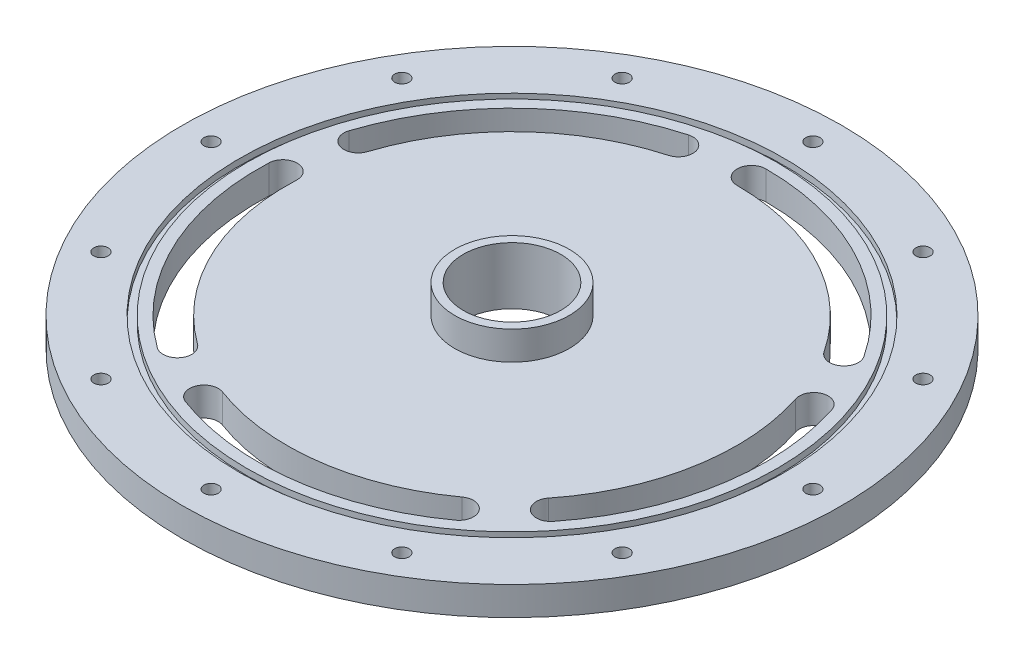
SolidWorks part; units mm, degrees
ref_plane "Front Plane" through (0, 0, 0) normal (0, 0, 1) x (1, 0, 0)
ref_plane "Top Plane" through (0, 0, 0) normal (0, 1, 0) x (1, 0, 0)
ref_plane "Right Plane" through (0, 0, 0) normal (1, 0, 0) x (0, 0, -1)
sketch "Sketch1" plane through (0, 0, 0) normal (0, 1, 0) x (1, 0, 0)
  circle A0 centre (0, 0) radius 146.05
  circle A1 centre (0, 0) radius 21.59
  circle A2 centre (0, 133.35) radius 3.175
  circle A3 centre (66.675, 115.4845) radius 3.175
  circle A4 centre (115.4845, 66.675) radius 3.175
  circle A5 centre (133.35, 0) radius 3.175
  circle A6 centre (115.4845, -66.675) radius 3.175
  circle A7 centre (66.675, -115.4845) radius 3.175
  circle A8 centre (0, -133.35) radius 3.175
  circle A9 centre (-66.675, -115.4845) radius 3.175
  circle A10 centre (-115.4845, -66.675) radius 3.175
  circle A11 centre (-133.35, 0) radius 3.175
  circle A12 centre (-115.4845, 66.675) radius 3.175
  circle A13 centre (-66.675, 115.4845) radius 3.175
  point P4 (0, 133.35)
  point P31 (0, 0)
  dimension "D1" = 292.1
  dimension "D2" = 43.18
  dimension "D4" = 6.35
  dimension "D3" = 133.35
  dimension "D5" = 12
extrude "Boss-Extrude1" add sketch "Sketch1" along normal blind 12.7
sketch "Sketch2" plane through (0, 12.7, 0) normal (0, 1, 0) x (1, 0, 0)
  circle A0 centre (0, 0) radius 120.65
  circle A1 centre (0, 0) radius 117.475
  dimension "D1" = 241.3
  dimension "D2" = 234.95
extrude "Cut-Extrude1" cut sketch "Sketch2" against normal blind 2.794
sketch "Sketch3" plane through (0, 12.7, 0) normal (0, 1, 0) x (1, 0, 0)
  line L0 (0, 0) -> (83.1307, 55.1686) construction
  arc A0 (0, 106.1466) -> (88.4428, 58.6939) centre (0, 0) cw construction
  arc A1 (93.7549, 62.2192) -> (0, 112.522) centre (0, 0) ccw
  arc A2 (83.1307, 55.1686) -> (0, 99.7712) centre (0, 0) ccw
  arc A3 (83.1307, 55.1686) -> (93.7549, 62.2192) centre (88.4428, 58.6939) ccw
  arc A4 (0, 112.522) -> (0, 99.7712) centre (0, 106.1466) ccw
  arc A5 (78.1573, -62.014) -> (94.888, 30.831) centre (0, 0) ccw
  arc A6 (78.1573, -62.014) -> (88.1458, -69.9394) centre (83.1515, -65.9767) ccw
  arc A7 (107.0148, 34.7712) -> (94.888, 30.831) centre (100.9514, 32.8011) ccw
  arc A8 (88.1458, -69.9394) -> (107.0148, 34.7712) centre (0, 0) ccw
  arc A9 (100.9514, 32.8011) -> (83.1515, -65.9767) centre (0, 0) cw construction
  arc A10 (-34.8269, -93.4954) -> (58.644, -80.7166) centre (0, 0) ccw
  arc A11 (-34.8269, -93.4954) -> (-39.2777, -105.4441) centre (-37.0523, -99.4697) ccw
  arc A12 (66.1388, -91.0322) -> (58.644, -80.7166) centre (62.3914, -85.8744) ccw
  arc A13 (-39.2777, -105.4441) -> (66.1388, -91.0322) centre (0, 0) ccw
  arc A14 (62.3914, -85.8744) -> (-37.0523, -99.4697) centre (0, 0) cw construction
  arc A15 (-99.6815, 4.2307) -> (-58.644, -80.7166) centre (0, 0) ccw
  arc A16 (-99.6815, 4.2307) -> (-112.4208, 4.7713) centre (-106.0511, 4.501) ccw
  arc A17 (-66.1388, -91.0322) -> (-58.644, -80.7166) centre (-62.3914, -85.8744) ccw
  arc A18 (-112.4208, 4.7713) -> (-66.1388, -91.0322) centre (0, 0) ccw
  arc A19 (-62.3914, -85.8744) -> (-106.0511, 4.501) centre (0, 0) cw construction
  arc A20 (-26.7797, 96.11) -> (-94.888, 30.831) centre (0, 0) ccw
  arc A21 (-26.7797, 96.11) -> (-30.2021, 108.393) centre (-28.4909, 102.2515) ccw
  arc A22 (-107.0148, 34.7712) -> (-94.888, 30.831) centre (-100.9514, 32.8011) ccw
  arc A23 (-30.2021, 108.393) -> (-107.0148, 34.7712) centre (0, 0) ccw
  arc A24 (-100.9514, 32.8011) -> (-28.4909, 102.2515) centre (0, 0) cw construction
  point P0 (0, 106.1466)
  point P36 (0, -0.3823)
  point P38 (50.1844, 93.5341)
  point P48 (104.464, -18.8245)
  point P55 (14.378, -105.1683)
  point P62 (-95.578, -46.1731)
  point P69 (-73.4484, 76.6318)
  dimension "D2" = 112.522
  dimension "D3" = 99.7712
  dimension "D5" = 5
extrude "Cut-Extrude2" cut sketch "Sketch3" against normal through all
sketch "Sketch5" plane through (0, 12.7, 0) normal (0, 1, 0) x (1, 0, 0)
  circle A0 centre (0, 0) radius 21.59
  circle A1 centre (0, 0) radius 25.4
  dimension "D1" = 43.18
  dimension "D2" = 50.8
extrude "Boss-Extrude2" add sketch "Sketch5" along normal blind 12.7
